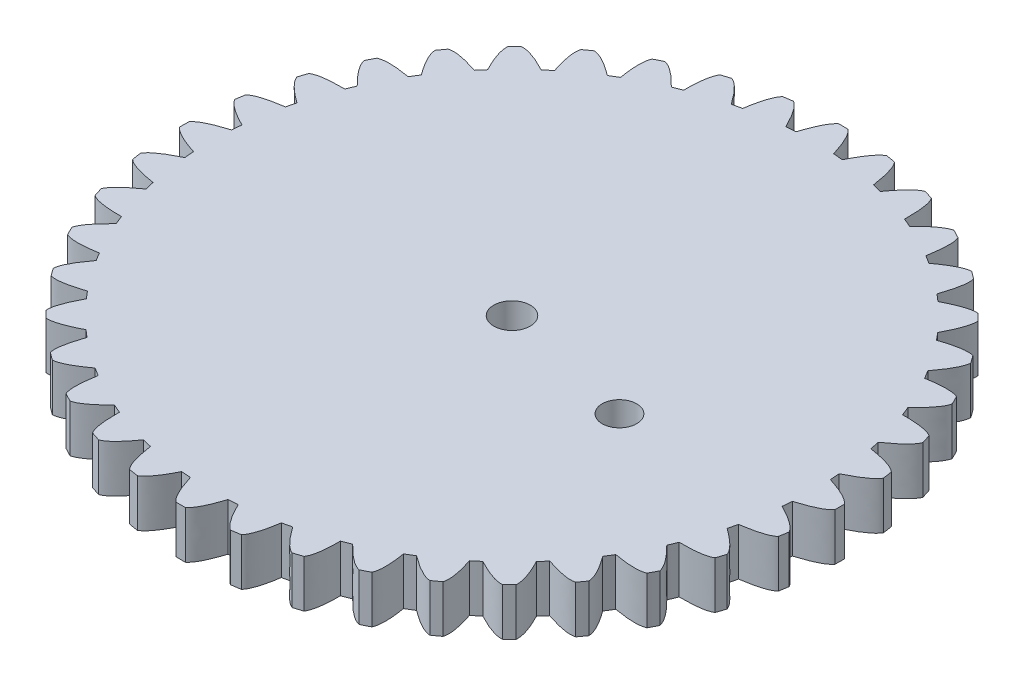
SolidWorks part; units mm, degrees
material "ABS"
ref_plane "Front Plane" through (0, 0, 0) normal (0, 0, 1) x (1, 0, 0)
ref_plane "Top Plane" through (0, 0, 0) normal (0, 1, 0) x (1, 0, 0)
ref_plane "Right Plane" through (0, 0, 0) normal (1, 0, 0) x (0, 0, -1)
sketch "Sketch1" plane through (0, 0, 0) normal (0, 1, 0) x (1, 0, 0)
  line L0 (21.1871, 23.7554) -> (23.9973, 20.9127) construction
  line L2 (22.5922, 22.334) -> (24.7257, 24.4431) construction
  line L3 (24.7257, 24.4431) -> (24.8654, 24.5812)
  circle A0 centre (0, 0) radius 31.831
  circle A1 centre (0, 0) radius 34.7682
  spline S0 degree 2 poles (23.9973, 20.9127) (27.1386, 26.8284) (21.1871, 23.7554) knots 0 0 0 1 1 1
  point P3 (21.1871, 23.7554)
  point P4 (23.9973, 20.9127)
  point P6 (24.3716, 24.7962)
  point P12 (20.4304, 24.4092)
  point P14 (24.8654, 24.5812)
  point P15 (25.0746, 24.085)
  point P16 (13.455, 28.8474)
  dimension "D1" = 63.662
  dimension "D4" = 3
  dimension "D5" = 1
  dimension "D2" = 4
  dimension "D3" = 1
extrude "Boss-Extrude4" add sketch "Sketch1" along normal blind 5 contours A0 | A0 S0 A1 region at (23.4992, 0, -23.2307) region at (0, 0, 0)
pattern_circular "CirPattern6" count 40 every 9 about axis through (0, 5, 0) along (0, 1, 0) of "Boss-Extrude4"
sketch "Sketch2" plane through (0, 5, 0) normal (0, 1, 0) x (1, 0, 0)
  circle A0 centre (0, 0) radius 1.925
  dimension "D1" = 3.85
extrude "Cut-Extrude2" cut sketch "Sketch2" against normal blind 10 contours A0 region at (0, 5, 0)
sketch "Sketch4" plane through (0, 0, 0) normal (0, -1, 0) x (1, 0, 0)
  circle A0 centre (14.633, 3.2977) radius 1.825
  dimension "D1" = 15
  dimension "D2" = 3.65
extrude "Cut-Extrude3" cut sketch "Sketch4" against normal blind 10
equation "\"number-of-teeth\"= 40"
equation "\"gear-size\"= 4mm"
equation "\"circumference\"= \"number-of-teeth\" * ( ( 1 + \"space-between-teeth\" ) * \"gear-size\" )"
equation "\"space-between-teeth\"= .25"
equation "\"D1@Sketch1\" = \"circumference\" / pi"
equation "\"D2@Sketch1\"=\"gear-size\""
equation "\"gear-length\"= 3mm"
equation "\"D4@Sketch1\"=\"gear-length\""
equation "\"D5@Sketch1\"=\"gear-size\" * \"space-between-teeth\""
equation "\"D3@Sketch1\"=\"gear-size\" * \"space-between-teeth\""
equation "\"D1@CirPattern6\"=\"number-of-teeth\""
equation "\"D2@CirPattern6\"=360 / \"number-of-teeth\""
